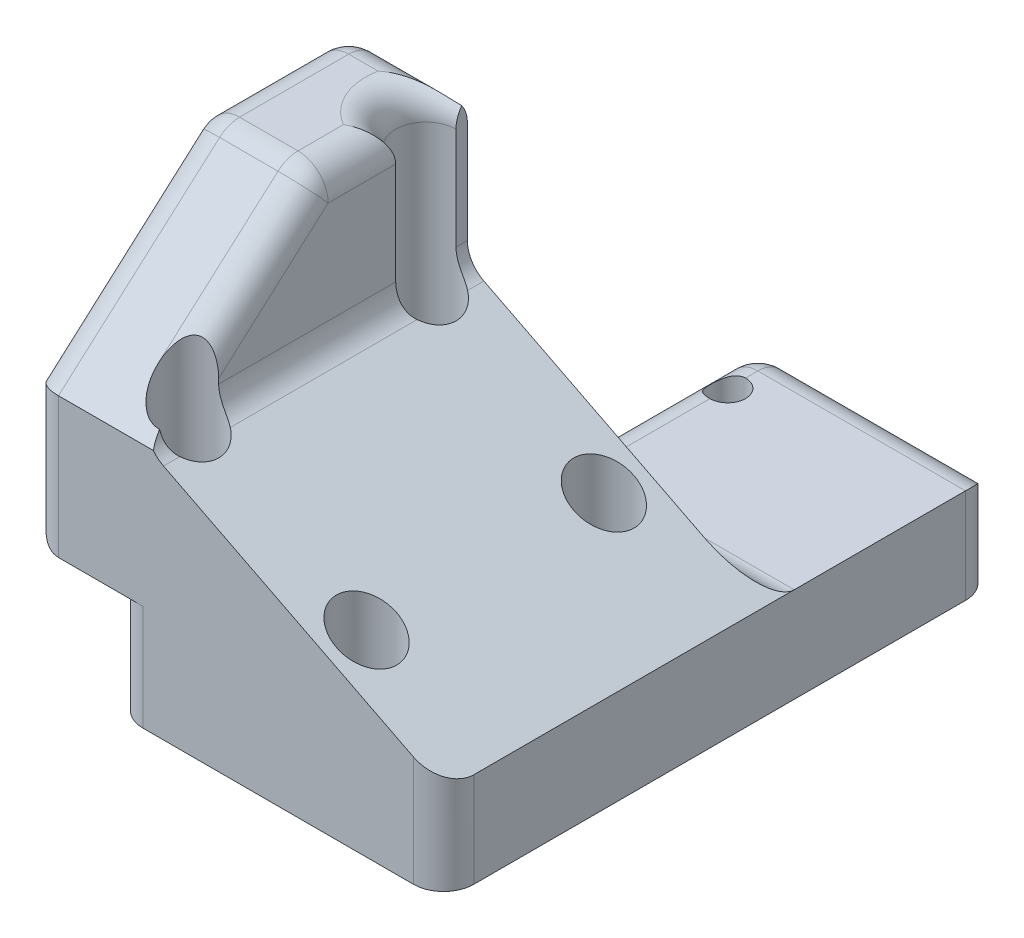
SolidWorks part; units mm, degrees
material "PLA"
ref_plane "Front Plane" through (0, 0, 0) normal (0, 0, 1) x (1, 0, 0)
ref_plane "Top Plane" through (0, 0, 0) normal (0, 1, 0) x (1, 0, 0)
ref_plane "Right Plane" through (0, 0, 0) normal (1, 0, 0) x (0, 0, -1)
sketch "Sketch1" plane through (0, 0, 0) normal (0, 1, 0) x (1, 0, 0)
  line L0 (-7.5, 10) -> (-7.5, -10) construction
  line L1 (-17.5, -13.5) -> (17.5, -13.5)
  line L2 (-17.5, -13.5) -> (-17.5, 13.5)
  line L3 (-17.5, 13.5) -> (17.5, 13.5)
  line L4 (17.5, -13.5) -> (17.5, 13.5)
  line L5 (-17.5, -13.5) -> (17.5, 13.5) construction
  line L6 (-17.5, 13.5) -> (17.5, -13.5) construction
  line L7 (-7.5, -10) -> (-7.5, 10) construction
  line L8 (-7.5, 10) -> (7.5, 10) construction
  line L9 (7.5, 10) -> (7.5, -10) construction
  line L10 (7.5, -10) -> (-7.5, -10) construction
  circle A0 centre (-7.5, 10) radius 1.5
  circle A1 centre (7.5, 10) radius 1.5
  circle A2 centre (7.5, -10) radius 1.5
  circle A3 centre (-7.5, -10) radius 1.5
  point P0 (0, 0)
  point P19 (0, 10)
  point P20 (7.5, 0)
  dimension "D3" = 3
  dimension "D1" = 15
  dimension "D2" = 20
  dimension "D4" = 35
  dimension "D5" = 27
extrude "Boss-Extrude1" add sketch "Sketch1" along normal mid plane 8
sketch "Sketch5" plane through (0, 4, 0) normal (0, 1, 0) x (1, 0, 0)
  line L0 (-17.5, 13.5) -> (-17.5, -13.5) construction
  line L1 (17.5, 13.5) -> (-17.5, 13.5)
  line L2 (17.5, 13.5) -> (17.5, 33.02)
  line L3 (17.5, 33.02) -> (-17.5, 33.02)
  line L4 (-17.5, 13.5) -> (-17.5, 33.02)
  line L5 (-17.5, 27.94) -> (17.5, 27.94) construction
  dimension "D1" = 27.94
  dimension "D2" = 5.08
extrude "Boss-Extrude3" add sketch "Sketch5" against normal through all
sketch "Sketch3" plane through (-17.5, 0, 0) normal (-1, 0, 0) x (0, 0, 1)
  line L0 (-13.5, 4) -> (13.5, 4)
  line L1 (13.5, 4) -> (13.5, 16.7)
  line L2 (13.5, 16.7) -> (-0.8, 29.4)
  line L3 (-0.8, 29.4) -> (-13.5, 29.4)
  line L8 (-33.02, 4) -> (13.5, 4) construction
  line L9 (-13.5, 29.4) -> (-13.5, 4)
  dimension "D1" = 12.7
  dimension "D2" = 12.7
  dimension "D3" = 12.7
  dimension "D4" = 27
extrude "Boss-Extrude2" add sketch "Sketch3" against normal blind 10
sketch "Sketch12" plane through (0, 0, 13.5) normal (0, 0, 1) x (1, 0, 0)
  line L0 (-7.5, 4) -> (17.5, 4)
  line L1 (17.5, 4) -> (-7.5, 16.7)
  line L2 (-7.5, 16.7) -> (-7.5, 29.4) construction
  line L3 (-7.5, 16.7) -> (-7.5, 4)
  line L4 (-7.5, 29.4) -> (-17.5, 29.4) construction
  dimension "D1" = 12.7
extrude "Boss-Extrude5" add sketch "Sketch12" against normal up to surface (27 mm away) up to face at (-12.5, 16.7, -13.5)
sketch "Sketch4" plane through (0, 4, 0) normal (0, -1, 0) x (1, 0, 0)
  circle A0 centre (-7.5, 10) radius 2.54
  circle A1 centre (-7.5, -10) radius 2.54
  circle A2 centre (7.5, 10) radius 2.54
  circle A3 centre (7.5, -10) radius 2.54
  dimension "D1" = 5.08
extrude "Cut-Extrude1" cut sketch "Sketch4" against normal through all
sketch "Sketch6" plane through (0, 4, 0) normal (0, 1, 0) x (1, 0, 0)
  line L0 (0, 27.94) -> (0, 0) construction
  circle A0 centre (0, 27.94) radius 1.5
  dimension "D2" = 3
  dimension "D1" = 27.94
extrude "Cut-Extrude2" cut sketch "Sketch6" against normal through all
sketch "Sketch7" plane through (0, 4, 0) normal (0, 1, 0) x (1, 0, 0)
  line L0 (17.5, 33.02) -> (-17.5, 33.02) construction
  line L1 (-17.5, 13.5) -> (-2.54, 13.5)
  line L2 (-17.5, 13.5) -> (-17.5, 33.02)
  line L3 (-17.5, 33.02) -> (-2.54, 33.02)
  line L4 (-2.54, 13.5) -> (-2.54, 33.02)
  circle A0 centre (0, 27.94) radius 1.5 construction
  dimension "D1" = 2.54
extrude "Cut-Extrude3" cut sketch "Sketch7" against normal through all
sketch "Sketch8" plane through (0, -4, 0) normal (0, -1, 0) x (1, 0, 0)
  line L0 (-17.5, 13.5) -> (17.5, 13.5) construction
  line L1 (-17.5, -13.5) -> (-10.388, -13.5)
  line L2 (-17.5, -13.5) -> (-17.5, 13.5)
  line L3 (-17.5, 13.5) -> (-10.388, 13.5)
  line L4 (-10.388, -13.5) -> (-10.388, 13.5)
  dimension "D1" = 7.112
extrude "Cut-Extrude4" cut sketch "Sketch8" against normal blind 8.89
fillet "Fillet5" radius 2.54 22 edges at (-7.5, 16.7, -13.02) (-7.5, 16.7, 13.02) (-7.5, 16.7, 0) (-2.54, 0, -13.5) (-7.5, 29.4, -4.13) (-12.5, 29.4, -0.8) (-17.5, 29.4, -7.15) (-12.5, 29.4, -13.5) (-10.04, 29.4, -10) (-10.388, 0.445, 13.5) (-10.388, 0.445, -13.5) (-17.5, 17.145, -13.5) (-17.5, 4.89, 0) (-17.5, 10.795, 13.5) (-17.5, 23.05, 6.35) (-7.5, 25.7321, 3.33) (7.48, 4, -13.5) (-2.54, 4, -23.26) (7.48, 4, -33.02) (-2.54, 0, -33.02) (17.5, 0, -33.02) (17.5, 0, 13.5)
